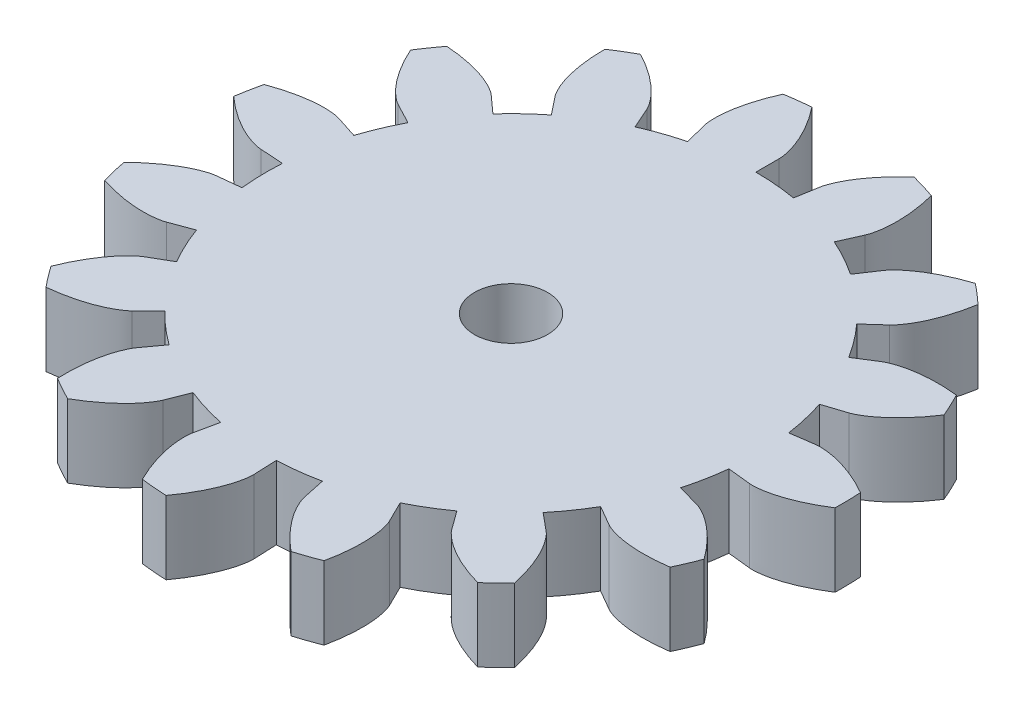
SolidWorks part; units mm, degrees
ref_plane "Front Plane" through (0, 0, 0) normal (0, 0, 1) x (1, 0, 0)
ref_plane "Top Plane" through (0, 0, 0) normal (0, 1, 0) x (1, 0, 0)
ref_plane "Right Plane" through (0, 0, 0) normal (1, 0, 0) x (0, 0, -1)
sketch "Reference attributes" plane through (0, 0, 0) normal (0, 1, 0) x (1, 0, 0)
  line L0 (0, 0) -> (15, 0) construction
  line L1 (0, -10) -> (1.56, -10) construction
  line L2 (0, 0) -> (14.4889, 3.8823) construction
  line L3 (0, 0) -> (14.0954, 5.1303) construction
  dimension "Teeth" = 15
  dimension "Module" = 1.56
  dimension "D2" = 10
  dimension "Helix Angle" = 15
  dimension "Pressure angle" = 20
sketch "Gear billet" plane through (0, 0, 0) normal (0, 1, 0) x (1, 0, 0)
  circle A0 centre (0, 0) radius 13.5525
  dimension "OuterDi" = 27.105
extrude "Gear billet Extrude" add sketch "Gear billet" along normal blind 3
ref_plane "Opposite gear face" through (0, 3, 0) normal (0, 1, 0) x (1, 0, 0)
ref_point "Twist centre point top"
ref_point "Twist centre point bottom"
ref_axis "Axis" through (0, 3, 0) along (0, -1, 0)
sketch "Involute Profile" plane through (0, 3, 0) normal (0, 1, 0) x (1, 0, 0)
  line L0 (0, 0) -> (0, 10.9944) construction
  line L1 (0, 0) -> (1.849, 10.8378) construction
  circle A0 centre (0, 0) radius 11.9925
  circle A4 centre (0, 0) radius 10.9944 construction
  spline S0 degree 4 poles (0, 10.9944) (0, 11.0283) (-0.0045, 11.1233) (-0.0311, 11.3029) (-0.0996, 11.5898) (-0.2249, 11.9512) (-0.4271, 12.399) (-0.7134, 12.8988) (-1.0767, 13.4167) (-1.516, 13.9384) (-1.9949, 14.4236) (-2.5074, 14.8731) (-3.0755, 15.3079) (-3.813, 15.7984) (-4.7381, 16.3098) (-5.863, 16.8014) (-7.1615, 17.2214) (-8.4917, 17.521) (-9.8443, 17.7042) (-11.2043, 17.778) (-12.5705, 17.7443) (-13.9226, 17.6133) (-15.2752, 17.381) (-16.4204, 17.107) (-17.4229, 16.8036) (-18.1317, 16.5596) (-18.7551, 16.3215) (-19.1642, 16.1543) (-19.7367, 15.9077) (-20.1624, 15.7055) (-20.5874, 15.5001) (-20.7978, 15.3881) (-20.9344, 15.3182) knots 0 0 0 0 0 0.005604 0.015718 0.02996 0.048734 0.068727 0.096889 0.125051 0.153212 0.181374 0.209535 0.237696 0.271429 0.327752 0.384075 0.440398 0.496721 0.553044 0.609367 0.66569 0.722013 0.778336 0.834659 0.86282 0.890982 0.909091 0.931818 0.954545 0.977273 1 1 1 1 1 construction
  spline S1 degree 4 poles (0, 10.9944) (0, 11.0283) (-0.0045, 11.1233) (-0.0311, 11.3029) (-0.0996, 11.5898) (-0.2249, 11.9512) (-0.4271, 12.399) (-0.7134, 12.8988) (-1.0767, 13.4167) (-1.516, 13.9384) (-1.9949, 14.4236) (-2.5074, 14.8731) (-3.0755, 15.3079) (-3.813, 15.7984) (-4.7381, 16.3098) (-5.863, 16.8014) (-7.1615, 17.2214) (-8.4917, 17.521) (-9.8443, 17.7042) (-11.2043, 17.778) (-12.5705, 17.7443) (-13.9226, 17.6133) (-15.2752, 17.381) (-16.4204, 17.107) (-17.4229, 16.8036) (-18.1317, 16.5596) (-18.6093, 16.3772) (-18.8455, 16.2833) (-18.9377, 16.2458) knots 0 0 0 0 0 0.005604 0.015718 0.02996 0.048734 0.068727 0.096889 0.125051 0.153212 0.181374 0.209535 0.237696 0.271429 0.327752 0.384075 0.440398 0.496721 0.553044 0.609367 0.66569 0.722013 0.778336 0.834659 0.86282 0.890982 0.909091 0.909091 0.909091 0.909091 0.909091
  spline S2 degree 4 poles (1.849, 10.8378) (1.8547, 10.8713) (1.8751, 10.9641) (1.9315, 11.1367) (2.0473, 11.408) (2.2315, 11.7431) (2.5062, 12.1506) (2.8725, 12.5951) (3.3177, 13.0446) (3.8384, 13.4849) (4.3921, 13.8827) (4.9729, 14.2396) (5.606, 14.5727) (6.4156, 14.9322) (7.4135, 15.2807) (8.6051, 15.5761) (9.9557, 15.7718) (11.3173, 15.8434) (12.6814, 15.7965) (14.0345, 15.6405) (15.3756, 15.3776) (16.6863, 15.021) (17.9807, 14.5645) (19.0634, 14.1019) (20.0006, 13.6343) (20.6584, 13.2745) (21.2328, 12.9349) (21.608, 12.7013) (22.1309, 12.362) (22.5164, 12.0911) (22.9009, 11.8171) (23.0895, 11.6713) (23.2123, 11.5794) knots 0 0 0 0 0 0.005604 0.015718 0.02996 0.048734 0.068727 0.096889 0.125051 0.153212 0.181374 0.209535 0.237696 0.271429 0.327752 0.384075 0.440398 0.496721 0.553044 0.609367 0.66569 0.722013 0.778336 0.834659 0.86282 0.890982 0.909091 0.931818 0.954545 0.977273 1 1 1 1 1 construction
  spline S3 degree 4 poles (1.849, 10.8378) (1.8547, 10.8713) (1.8751, 10.9641) (1.9315, 11.1367) (2.0473, 11.408) (2.2315, 11.7431) (2.5062, 12.1506) (2.8725, 12.5951) (3.3177, 13.0446) (3.8384, 13.4849) (4.3921, 13.8827) (4.9729, 14.2396) (5.606, 14.5727) (6.4156, 14.9322) (7.4135, 15.2807) (8.6051, 15.5761) (9.9557, 15.7718) (11.3173, 15.8434) (12.6814, 15.7965) (14.0345, 15.6405) (15.3756, 15.3776) (16.6863, 15.021) (17.9807, 14.5645) (19.0634, 14.1019) (20.0006, 13.6343) (20.6584, 13.2745) (21.0985, 13.0144) (21.3155, 12.8821) (21.4001, 12.8296) knots 0 0 0 0 0 0.005604 0.015718 0.02996 0.048734 0.068727 0.096889 0.125051 0.153212 0.181374 0.209535 0.237696 0.271429 0.327752 0.384075 0.440398 0.496721 0.553044 0.609367 0.66569 0.722013 0.778336 0.834659 0.86282 0.890982 0.909091 0.909091 0.909091 0.909091 0.909091
  point P6 (-0.2494, 11.9899)
  point P11 (2.2623, 11.7772)
  dimension "BaseDi" = 21.9888
  dimension "Adjusted Reference Diameter" = 23.985
  dimension "Reference Circumferential pitch" = 2.5117
sketch "Tooth profile" plane through (0, 3, 0) normal (0, 1, 0) x (1, 0, 0)
  line L0 (0, 0) -> (0, 10.9944) construction
  line L1 (0, 0) -> (1.849, 10.8378) construction
  line L2 (0, 0) -> (0, 10.9944)
  line L3 (0, 0) -> (1.849, 10.8378)
  line L4 (-0.2, -2.3616) -> (-0.2, 10.9944) construction
  line L5 (-0.2, -2.3616) -> (2.0461, 10.8042) construction
  circle A0 centre (0, 0) radius 13.5525 construction
  circle A1 centre (0, 0) radius 13.5525
  circle A2 centre (0, 0) radius 10.0425
  spline S0 degree 1 poles (-0.2, 10.9944) (-18.8625, 16.0605) knots 0 0 1 1 construction
  spline S1 degree 4 poles (-999.2468, 47.0982) (-31.7113, 6.7197) (-0.7279, 7.7269) (0.3375, 9.7591) (-0.0996, 11.5898) (-0.2249, 11.9512) (-0.4271, 12.399) (-0.7134, 12.8988) (-1.0767, 13.4167) (-1.516, 13.9384) (-1.9949, 14.4236) (-2.5074, 14.8731) (-3.0755, 15.3079) (-3.813, 15.7984) (-4.7381, 16.3098) (-5.863, 16.8014) (-7.1615, 17.2214) (-8.4917, 17.521) (-9.8443, 17.7042) (-11.2043, 17.778) (-12.5705, 17.7443) (-13.9226, 17.6133) (-15.2752, 17.381) (-16.4204, 17.107) (-17.4229, 16.8036) (-19.633, 16.0429) (-23.1881, 14.4164) (2.5893, 24.4855) (-944.9717, -360.906) knots -0.26224 -0.26224 -0.26224 -0.26224 -0.26224 0.005604 0.015718 0.02996 0.048734 0.068727 0.096889 0.125051 0.153212 0.181374 0.209535 0.237696 0.271429 0.327752 0.384075 0.440398 0.496721 0.553044 0.609367 0.66569 0.722013 0.778336 0.834659 0.86282 0.890982 1.186013 1.186013 1.186013 1.186013 1.186013 only from (0, 10.9944) to (-18.9377, 16.2458) construction
  spline S2 degree 4 poles (992.9358, -121.6178) (32.3898, 1.291) (2.017, 7.4944) (1.3085, 9.6768) (2.0473, 11.408) (2.2315, 11.7431) (2.5062, 12.1506) (2.8725, 12.5951) (3.3177, 13.0446) (3.8384, 13.4849) (4.3921, 13.8827) (4.9729, 14.2396) (5.606, 14.5727) (6.4156, 14.9322) (7.4135, 15.2807) (8.6051, 15.5761) (9.9557, 15.7718) (11.3173, 15.8434) (12.6814, 15.7965) (14.0345, 15.6405) (15.3756, 15.3776) (16.6863, 15.021) (17.9807, 14.5645) (19.0634, 14.1019) (20.0006, 13.6343) (22.0514, 12.5127) (25.2823, 10.3115) (1.5654, 24.5722) (870.8189, -514.6836) knots -0.26224 -0.26224 -0.26224 -0.26224 -0.26224 0.005604 0.015718 0.02996 0.048734 0.068727 0.096889 0.125051 0.153212 0.181374 0.209535 0.237696 0.271429 0.327752 0.384075 0.440398 0.496721 0.553044 0.609367 0.66569 0.722013 0.778336 0.834659 0.86282 0.890982 1.186013 1.186013 1.186013 1.186013 1.186013 only from (1.849, 10.8378) to (21.4001, 12.8296) construction
  spline S3 degree 1 poles (2.0461, 10.8042) (21.2947, 12.6596) knots 0 0 1 1 construction
  spline S4 degree 4 poles (0, 10.9944) (0, 11.0283) (-0.0045, 11.1233) (-0.0311, 11.3029) (-0.0996, 11.5898) (-0.2249, 11.9512) (-0.4271, 12.399) (-0.7134, 12.8988) (-1.0767, 13.4167) (-1.516, 13.9384) (-1.9949, 14.4236) (-2.5074, 14.8731) (-3.0755, 15.3079) (-3.813, 15.7984) (-4.7381, 16.3098) (-5.863, 16.8014) (-7.1615, 17.2214) (-8.4917, 17.521) (-9.8443, 17.7042) (-11.2043, 17.778) (-12.5705, 17.7443) (-13.9226, 17.6133) (-15.2752, 17.381) (-16.4204, 17.107) (-17.4229, 16.8036) (-18.1317, 16.5596) (-18.6093, 16.3772) (-18.8455, 16.2833) (-18.9377, 16.2458) knots 0 0 0 0 0 0.005604 0.015718 0.02996 0.048734 0.068727 0.096889 0.125051 0.153212 0.181374 0.209535 0.237696 0.271429 0.327752 0.384075 0.440398 0.496721 0.553044 0.609367 0.66569 0.722013 0.778336 0.834659 0.86282 0.890982 0.909091 0.909091 0.909091 0.909091 0.909091
  spline S5 degree 4 poles (1.849, 10.8378) (1.8547, 10.8713) (1.8751, 10.9641) (1.9315, 11.1367) (2.0473, 11.408) (2.2315, 11.7431) (2.5062, 12.1506) (2.8725, 12.5951) (3.3177, 13.0446) (3.8384, 13.4849) (4.3921, 13.8827) (4.9729, 14.2396) (5.606, 14.5727) (6.4156, 14.9322) (7.4135, 15.2807) (8.6051, 15.5761) (9.9557, 15.7718) (11.3173, 15.8434) (12.6814, 15.7965) (14.0345, 15.6405) (15.3756, 15.3776) (16.6863, 15.021) (17.9807, 14.5645) (19.0634, 14.1019) (20.0006, 13.6343) (20.6584, 13.2745) (21.0985, 13.0144) (21.3155, 12.8821) (21.4001, 12.8296) knots 0 0 0 0 0 0.005604 0.015718 0.02996 0.048734 0.068727 0.096889 0.125051 0.153212 0.181374 0.209535 0.237696 0.271429 0.327752 0.384075 0.440398 0.496721 0.553044 0.609367 0.66569 0.722013 0.778336 0.834659 0.86282 0.890982 0.909091 0.909091 0.909091 0.909091 0.909091
  spline S6 degree 3 poles (-18.8625, 16.0605) (-18.763, 16.1009) (-18.5732, 16.1761) (-18.1131, 16.3514) (-17.3753, 16.6105) (-15.8458, 17.0676) (-13.6187, 17.4947) (-10.8943, 17.6198) (-8.1871, 17.3152) (-5.5764, 16.5417) (-3.5762, 15.4725) (-2.1712, 14.3454) (-1.2532, 13.3589) (-0.6406, 12.4264) (-0.306, 11.6027) (-0.2, 11.2021) (-0.2, 10.9944) knots 0 0 0 0 0.014205 0.028409 0.056818 0.113636 0.227273 0.340909 0.454545 0.568182 0.681818 0.738636 0.795455 0.852273 0.880682 0.909091 0.909091 0.909091 0.909091 construction
  spline S7 degree 3 poles (2.0461, 10.8042) (2.081, 11.0089) (2.2529, 11.386) (2.7212, 12.1417) (3.482, 12.9579) (4.5527, 13.7759) (6.1273, 14.6507) (8.2788, 15.3683) (10.9824, 15.6918) (13.7023, 15.5368) (16.3669, 14.9552) (18.4904, 14.1597) (19.9212, 13.4519) (20.605, 13.0724) (21.029, 12.8222) (21.2035, 12.7162) (21.2947, 12.6596) knots 0 0 0 0 0.028409 0.056818 0.113636 0.170455 0.227273 0.340909 0.454545 0.568182 0.681818 0.795455 0.852273 0.880682 0.894886 0.909091 0.909091 0.909091 0.909091 construction
  dimension "RootDi" = 20.085
  dimension "Offset" = 0.2
extrude "Cut tooth profile" cut sketch "Tooth profile" against normal up to next contours A1 region at (1.0201, 3, -12.0452)
sketch "Tooth profile OFFSET" plane through (0, 3, 0) normal (0, 1, 0) x (1, 0, 0)
  line L4 (-0.1, -1.1808) -> (-0.1, 10.9944)
  line L5 (1.9475, 10.821) -> (-0.1, -1.1808)
  line L6 (-0.1, -1.1808) -> (-0.1, 10.9944)
  line L7 (1.9475, 10.821) -> (-0.1, -1.1808)
  circle A3 centre (0, 0) radius 13.5525 construction
  circle A4 centre (0, 0) radius 13.5525
  circle A6 centre (0, 0) radius 9.9425
  circle A7 centre (0, 0) radius 9.9425
  spline S4 degree 3 poles (1716.7359, -1048.0475) (-1.9946, 22.8241) (27.5954, 9.0093) (20.9727, 12.9716) (20.8678, 13.0334) (20.66, 13.1538) (20.5572, 13.2121) (20.3571, 13.3234) (20.2592, 13.3767) (19.7664, 13.6395) (19.3517, 13.8452) (18.5188, 14.2232) (18.1005, 14.3955) (17.2469, 14.7143) (16.8128, 14.86) (15.5017, 15.2468) (14.6091, 15.4413) (12.8042, 15.6881) (11.8918, 15.7402) (10.0722, 15.6837) (9.1646, 15.5752) (7.3899, 15.1774) (6.5221, 14.8882) (4.8834, 14.1062) (4.11, 13.6136) (3.1065, 12.7007) (2.7981, 12.3674) (2.4031, 11.8205) (2.2825, 11.6302) (2.1283, 11.3333) (2.0815, 11.2323) (-0.0855, 5.7491) (12.1344, -4.0363) (1885.5507, 682.7932) knots -1.021392 -1.021392 -1.021392 -1.021392 0.015625 0.015625 0.03125 0.03125 0.046875 0.046875 0.0625 0.0625 0.125 0.125 0.1875 0.1875 0.25 0.25 0.375 0.375 0.5 0.5 0.625 0.625 0.75 0.75 0.875 0.875 0.9375 0.9375 0.96875 0.96875 0.984375 0.984375 1.801746 1.801746 1.801746 1.801746 only from (21.3474, 12.7446) to (1.9475, 10.821)
  spline S5 degree 3 poles (-1743.85, 990.1541) (-12.6403, -1.9381) (1.0511, 5.6529) (-0.1629, 11.4224) (-0.1921, 11.5298) (-0.2941, 11.8485) (-0.381, 12.0563) (-0.6784, 12.6618) (-0.9263, 13.0422) (-1.762, 14.1109) (-2.4416, 14.7266) (-3.9255, 15.773) (-4.7322, 16.204) (-6.4147, 16.8946) (-7.2912, 17.1542) (-9.0754, 17.5159) (-9.9835, 17.618) (-11.8042, 17.6783) (-12.7168, 17.6366) (-14.0743, 17.4758) (-14.5268, 17.4052) (-15.4218, 17.2345) (-15.8631, 17.1349) (-16.7477, 16.9024) (-17.1911, 16.7694) (-17.7211, 16.5932) (-17.8266, 16.5572) (-18.0426, 16.4811) (-18.1536, 16.4408) (-18.3787, 16.3572) (-18.4925, 16.3139) (-25.6873, 13.5218) (5.8049, 22.1637) (-1868.5668, -744.4259) knots -0.801743 -0.801743 -0.801743 -0.801743 0.015625 0.015625 0.03125 0.03125 0.0625 0.0625 0.125 0.125 0.25 0.25 0.375 0.375 0.5 0.5 0.625 0.625 0.75 0.75 0.8125 0.8125 0.875 0.875 0.9375 0.9375 0.953125 0.953125 0.96875 0.96875 0.984375 0.984375 2.021397 2.021397 2.021397 2.021397 only from (-0.1, 10.9944) to (-18.9001, 16.1531)
  spline S6 degree 3 poles (21.3474, 12.7446) (21.2594, 12.7992) (21.1693, 12.854) (20.9727, 12.9716) (20.8678, 13.0334) (20.66, 13.1538) (20.5572, 13.2121) (20.3571, 13.3234) (20.2592, 13.3767) (19.7664, 13.6395) (19.3517, 13.8452) (18.5188, 14.2232) (18.1005, 14.3955) (17.2469, 14.7143) (16.8128, 14.86) (15.5017, 15.2468) (14.6091, 15.4413) (12.8042, 15.6881) (11.8918, 15.7402) (10.0722, 15.6837) (9.1646, 15.5752) (7.3899, 15.1774) (6.5221, 14.8882) (4.8834, 14.1062) (4.11, 13.6136) (3.1065, 12.7007) (2.7981, 12.3674) (2.4031, 11.8205) (2.2825, 11.6302) (2.1283, 11.3333) (2.0815, 11.2323) (2.0002, 11.0266) (1.9648, 10.9222) (1.9475, 10.821) knots 0 0 0 0 0.015625 0.015625 0.03125 0.03125 0.046875 0.046875 0.0625 0.0625 0.125 0.125 0.1875 0.1875 0.25 0.25 0.375 0.375 0.5 0.5 0.625 0.625 0.75 0.75 0.875 0.875 0.9375 0.9375 0.96875 0.96875 0.984375 0.984375 1 1 1 1
  spline S7 degree 3 poles (-0.1, 10.9944) (-0.1, 11.097) (-0.1173, 11.206) (-0.1629, 11.4224) (-0.1921, 11.5298) (-0.2941, 11.8485) (-0.381, 12.0563) (-0.6784, 12.6618) (-0.9263, 13.0422) (-1.762, 14.1109) (-2.4416, 14.7266) (-3.9255, 15.773) (-4.7322, 16.204) (-6.4147, 16.8946) (-7.2912, 17.1542) (-9.0754, 17.5159) (-9.9835, 17.618) (-11.8042, 17.6783) (-12.7168, 17.6366) (-14.0743, 17.4758) (-14.5268, 17.4052) (-15.4218, 17.2345) (-15.8631, 17.1349) (-16.7477, 16.9024) (-17.1911, 16.7694) (-17.7211, 16.5932) (-17.8266, 16.5572) (-18.0426, 16.4811) (-18.1536, 16.4408) (-18.3787, 16.3572) (-18.4925, 16.3139) (-18.7061, 16.231) (-18.8042, 16.1921) (-18.9001, 16.1531) knots 0 0 0 0 0.015625 0.015625 0.03125 0.03125 0.0625 0.0625 0.125 0.125 0.25 0.25 0.375 0.375 0.5 0.5 0.625 0.625 0.75 0.75 0.8125 0.8125 0.875 0.875 0.9375 0.9375 0.953125 0.953125 0.96875 0.96875 0.984375 0.984375 1 1 1 1
  line M3 (0, 10.0425) -> (0, 10.9944)
  spline M4 degree 4 poles (0, 10.9944) (0, 11.0283) (-0.0045, 11.1233) (-0.0311, 11.3029) (-0.0996, 11.5898) (-0.2249, 11.9512) (-0.4271, 12.399) (-0.7134, 12.8988) (-1.0767, 13.4167) (-1.516, 13.9384) (-1.9949, 14.4236) (-2.5074, 14.8731) (-3.0755, 15.3079) (-3.813, 15.7984) (-4.7381, 16.3098) (-5.863, 16.8014) (-7.1615, 17.2214) (-8.4917, 17.521) (-9.8443, 17.7042) (-11.2043, 17.778) (-12.5705, 17.7443) (-13.9226, 17.6133) (-15.2752, 17.381) (-16.4204, 17.107) (-17.4229, 16.8036) (-18.1317, 16.5596) (-18.6093, 16.3772) (-18.8455, 16.2833) (-18.9377, 16.2458) knots 0 0 0 0 0 0.005604 0.015718 0.02996 0.048734 0.068727 0.096889 0.125051 0.153212 0.181374 0.209535 0.237696 0.271429 0.327752 0.384075 0.440398 0.496721 0.553044 0.609367 0.66569 0.722013 0.778336 0.834659 0.86282 0.890982 0.909091 0.909091 0.909091 0.909091 0.909091 only from (0, 10.9944) to (-1.1598, 13.5028)
  arc M5 (-1.1598, 13.5028) -> (3.4141, 13.1154) centre (0, 0) ccw
  spline M6 degree 4 poles (21.4001, 12.8296) (21.3155, 12.8821) (21.0985, 13.0144) (20.6584, 13.2745) (20.0006, 13.6343) (19.0634, 14.1019) (17.9807, 14.5645) (16.6863, 15.021) (15.3756, 15.3776) (14.0345, 15.6405) (12.6814, 15.7965) (11.3173, 15.8434) (9.9557, 15.7718) (8.6051, 15.5761) (7.4135, 15.2807) (6.4156, 14.9322) (5.606, 14.5727) (4.9729, 14.2396) (4.3921, 13.8827) (3.8384, 13.4849) (3.3177, 13.0446) (2.8725, 12.5951) (2.5062, 12.1506) (2.2315, 11.7431) (2.0473, 11.408) (1.9315, 11.1367) (1.8751, 10.9641) (1.8547, 10.8713) (1.849, 10.8378) knots 0 0 0 0 0 0.018109 0.04627 0.074432 0.130755 0.187078 0.243401 0.299724 0.356047 0.41237 0.468693 0.525016 0.581339 0.637662 0.671395 0.699556 0.727717 0.755879 0.78404 0.812202 0.840364 0.860357 0.879131 0.893373 0.903487 0.909091 0.909091 0.909091 0.909091 0.909091 only from (3.4141, 13.1154) to (1.849, 10.8378)
  line M7 (1.849, 10.8378) -> (1.6889, 9.8995)
  arc M8 (1.6889, 9.8995) -> (0, 10.0425) centre (0, 0) ccw
  dimension "Offset" = 0.1
  dimension "D2" = 0.1
extrude "Cut Tooth profile OFFSET" [suppressed] cut sketch "Tooth profile OFFSET" against normal up to surface (10 mm away) contours S7 L6 A7 L7 S6 A4 M6 M7 M8 M3 M4 M5 up to face at (0.6212, 0, -7.3346)
sketch "Tangent meshing reference" plane through (0, 3, 0) normal (0, 1, 0) x (1, 0, 0)
  circle A0 centre (0, 0) radius 11.9925 construction
  circle A1 centre (0, 0) radius 11.9925
sketch "Gear ratio reference" plane through (0, 3, 0) normal (0, 1, 0) x (1, 0, 0)
  circle A0 centre (0, 0) radius 11.7
  dimension "Reference diameter" = 23.4
pattern_circular "Duplicate teeth" count 15 over 360 about axis through (0, 3, 0) along (0, -1, 0) of "Cut tooth profile"
other "Twist Left" [suppressed] parameters "D0"=3.84
other "Twist Right" [suppressed] parameters "D0"=3.84
mirror "Herringbone Mirror" [suppressed] about plane through (0, 3, 0) normal (0, 1, 0) of bodies 259
sketch "Sketch1" plane through (0, 3, 0) normal (0, 1, 0) x (1, 0, 0)
  circle A0 centre (0, 0) radius 1.5
  dimension "D1" = 3
extrude "Cut-Extrude1" cut sketch "Sketch1" against normal through all
equation "\"D1@Duplicate teeth\"=\"Teeth@Reference attributes\""
equation "\"twist\"= \"suppressed\""
equation "\"D2@Tooth profile OFFSET\"=\"Offset@Tooth profile OFFSET\""
